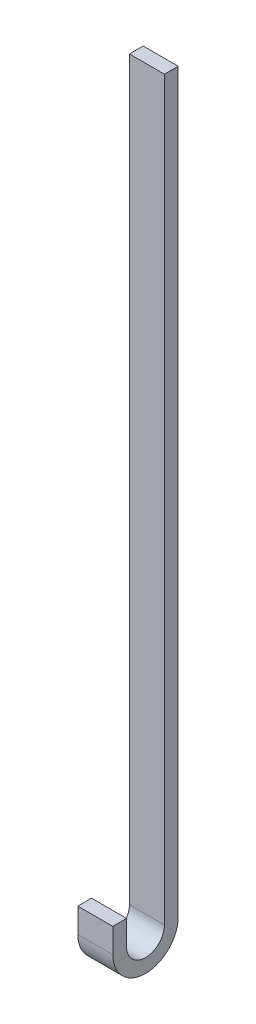
SolidWorks part; units mm, degrees
ref_plane "Front" through (0, 0, 0) normal (0, 0, 1) x (1, 0, 0)
ref_plane "Top" through (0, 0, 0) normal (0, 1, 0) x (1, 0, 0)
ref_plane "Right" through (0, 0, 0) normal (1, 0, 0) x (0, 0, -1)
sketch "Sketch1" plane through (0, 0, 0) normal (1, 0, 0) x (0, 0, -1)
  line L0 (0, 0) -> (0, -26.6925)
  line L1 (71.12, -26.6925) -> (71.12, 774.7)
  line L2 (14.986, 0) -> (14.986, -26.6925)
  line L3 (56.134, -26.6925) -> (56.134, 774.7)
  line L4 (0, 0) -> (14.986, 0)
  line L5 (56.134, 774.7) -> (71.12, 774.7)
  line L6 (148.336, 876.3) -> (97.536, 876.3) construction
  arc A0 (0, -26.6925) -> (71.12, -26.6925) centre (35.56, -26.6925) ccw
  arc A1 (14.986, -26.6925) -> (56.134, -26.6925) centre (35.56, -26.6925) ccw
  dimension "D1" = 939.8
  dimension "D2" = 71.12
  dimension "D4" = 41.148
  dimension "D5" = 101.6
  dimension "D3" = 14.986
extrude "Boss-Extrude1" add sketch "Sketch1" along normal blind 38.1
